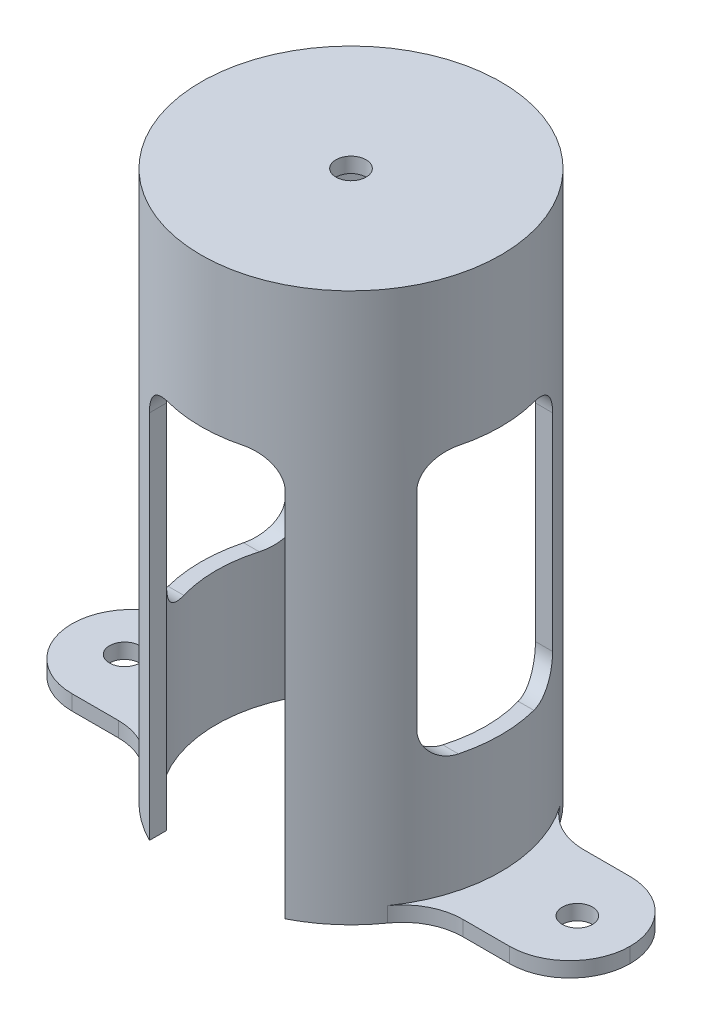
SolidWorks part; units mm, degrees
material "6061-T6 (SS)"
ref_plane "Front Plane" through (0, 0, 0) normal (0, 0, 1) x (1, 0, 0)
ref_plane "Top Plane" through (0, 0, 0) normal (0, 1, 0) x (1, 0, 0)
ref_plane "Right Plane" through (0, 0, 0) normal (1, 0, 0) x (0, 0, -1)
sketch "Sketch2" plane through (0, 0, 0) normal (0, 1, 0) x (1, 0, 0)
  circle A1 centre (0, 0) radius 9.9375
  dimension "D2" = 19.875
extrude "Boss-Extrude1" add sketch "Sketch2" along normal blind 35.384
sketch "Sketch4" plane through (0, 35.384, 0) normal (0, 1, 0) x (1, 0, 0)
  circle A0 centre (0, 0) radius 1
  dimension "D1" = 2
extrude "Cut-Extrude2" cut sketch "Sketch4" against normal through all
sketch "Sketch11" plane through (0, 0, 0) normal (0, -1, 0) x (1, 0, 0)
  line L0 (9.0969, 4) -> (18.5, 4)
  line L1 (-18.5, 4) -> (-9.0969, 4)
  line L2 (-18.5, 4) -> (-18.5, -4)
  line L3 (-18.5, -4) -> (-9.0969, -4)
  line L4 (18.5, 4) -> (18.5, -4)
  line L5 (-18.5, 4) -> (18.5, -4) construction
  line L6 (-18.5, -4) -> (18.5, 4) construction
  line L7 (9.0969, -4) -> (18.5, -4)
  arc A0 (9.0969, 4) -> (-9.0969, 4) centre (0, 0) ccw
  circle A1 centre (0, 0) radius 8.9375
  arc A2 (-9.0969, -4) -> (9.0969, -4) centre (0, 0) ccw
  point P0 (0, 0)
  dimension "D3" = 19.875
  dimension "D4" = 17.875
  dimension "D1" = 8
  dimension "D2" = 37
extrude "Boss-Extrude2" add sketch "Sketch11" along normal blind 1
sketch "Sketch12" plane through (0, 0, 0) normal (0, -1, 0) x (1, 0, 0)
  circle A0 centre (0, 0) radius 8.9375
  dimension "D1" = 17.875
extrude "Cut-Extrude7" cut sketch "Sketch12" against normal blind 34.384
ref_plane "Plane4" through (0, 0, 30) normal (0, 0, 1) x (1, 0, 0)
sketch "Sketch13" plane through (0, 0, 30) normal (0, 0, 1) x (1, 0, 0)
  line L0 (0, -10.9313) -> (0, 10.9313) construction
  line L1 (-4.5, 25.538) -> (4.5, 25.538)
  line L2 (-4.5, 25.538) -> (-4.5, -1)
  line L3 (-4.5, -1) -> (4.5, -1)
  line L4 (4.5, 25.538) -> (4.5, -1)
  line L5 (-4.5, 25.538) -> (4.5, -1) construction
  line L6 (-4.5, -1) -> (4.5, 25.538) construction
  line L7 (-9.0969, -1) -> (9.0969, -1) construction
  point P0 (0, 12.269)
  dimension "D1" = 26.538
  dimension "D2" = 9
extrude "Cut-Extrude8" cut sketch "Sketch13" against normal through all
ref_plane "Plane5" through (30, 0, 0) normal (1, 0, 0) x (0, 0, -1)
sketch "Sketch14" plane through (30, 0, 0) normal (1, 0, 0) x (0, 0, -1)
  line L0 (0, 10.9313) -> (0, -10.9313) construction
  line L1 (-4.5, 25.538) -> (4.5, 25.538)
  line L2 (-4.5, 25.538) -> (-4.5, 7.846)
  line L3 (-4.5, 7.846) -> (4.5, 7.846)
  line L4 (4.5, 25.538) -> (4.5, 7.846)
  line L5 (-4.5, 25.538) -> (4.5, 7.846) construction
  line L6 (-4.5, 7.846) -> (4.5, 25.538) construction
  line L7 (4, -1) -> (-4, -1) construction
  point P0 (0, 16.692)
  dimension "D2" = 9
  dimension "D1" = 17.692
  dimension "D3" = 17.692
extrude "Cut-Extrude9" cut sketch "Sketch14" against normal through all
fillet "Fillet3" radius 2 12 edges at (4.5, 25.538, -8.2911) (-4.5, 25.538, -8.2911) (-4.5, 25.538, 8.2911) (4.5, 25.538, 8.2911) (-8.2911, 25.538, 4.5) (-8.2911, 25.538, -4.5) (-8.2911, 7.846, -4.5) (-8.2911, 7.846, 4.5) (8.2911, 7.846, 4.5) (8.2911, 25.538, 4.5) (8.2911, 25.538, -4.5) (8.2911, 7.846, -4.5)
fillet "Fillet4" radius 4 8 edges at (9.0969, -0.5, -4) (18.5, -0.5, -4) (9.0969, -0.5, 4) (18.5, -0.5, 4) (-9.0969, -0.5, 4) (-18.5, -0.5, -4) (-9.0969, -0.5, -4) (-18.5, -0.5, 4)
sketch "Sketch15" plane through (0, 0, 0) normal (0, 1, 0) x (1, 0, 0)
  line L0 (-10.9313, 0) -> (10.9313, 0) construction
  circle A0 centre (-15, 0) radius 1
  circle A1 centre (15, 0) radius 1
  dimension "D1" = 15
  dimension "D2" = 15
extrude "Cut-Extrude10" cut sketch "Sketch15" against normal up to next
equation "\"FrangiboltTotalDiameter\"= 0.625in"
equation "\"FrangiboltTotalLength\"= 0.960in"
equation "\"FrangiboltThruHoleDiameter\"= 0.169in"
equation "\"EnclosureWallThickness\"= 1mm"
equation "\"EnclosureWallSpacing\"= 1mm"
equation "\"EnclosureInnerDiameter\"= \"FrangiboltTotalDiameter\" + 2 * \"EnclosureWallSpacing\""
equation "\"EnclosureOuterDiameter\"= \"FrangiboltTotalDiameter\" + 2 * \"EnclosureWallSpacing\" + 2 * \"EnclosureWallThickness\""
equation "\"EnclosureTotalLength\"= \"FrangiboltTotalLength\" + \"DamperLength\" + \"EnclosureWallThickness\""
equation "\"D2@Sketch2\"=\"EnclosureOuterDiameter\""
equation "\"D1@Boss-Extrude1\"=\"EnclosureTotalLength\""
equation "\"DamperLength\"= 10mm"
equation "\"EnclosureLip\"= 5mm"
equation "\"FrangiboltBoxWidth\"= 7mm"
equation "\"EnclosureMountingStandoff\"=37"
equation "\"D2@Sketch11\"=\"EnclosureMountingStandoff\""
equation "\"D3@Sketch11\"=\"EnclosureOuterDiameter\""
equation "\"D4@Sketch11\"=\"EnclosureInnerDiameter\""
equation "\"D1@Boss-Extrude2\"=\"EnclosureWallThickness\""
equation "\"D1@Sketch12\"=\"EnclosureInnerDiameter\""
equation "\"D1@Cut-Extrude7\"=\"EnclosureTotalLength\"-\"EnclosureWallThickness\""
equation "\"D1@Sketch13\"=\"EnclosureTotalLength\"*0.75"
equation "\"D2@Sketch13\"=\"FrangiboltBoxWidth\"+2mm"
equation "\"D1@Sketch14\"=\"EnclosureTotalLength\"*0.5"
equation "\"D2@Sketch14\"=\"FrangiboltBoxWidth\"+2mm"
equation "\"D3@Sketch14\"=\"EnclosureTotalLength\"*0.5"
equation "\"EnclosureMountingHoleDiameter\"= 2"
equation "\"D3@Sketch15\"=\"EnclosureMountingHoleDiameter\""
equation "\"D4@Sketch15\"=\"EnclosureMountingHoleDiameter\""
